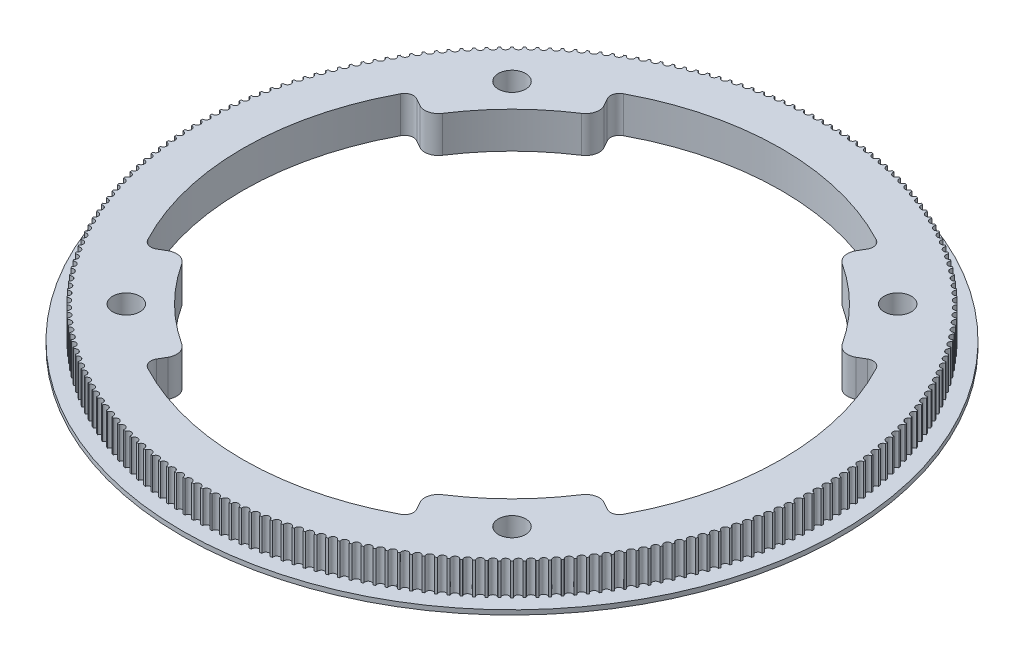
SolidWorks part; units mm, degrees
material "ABS"
ref_plane "Front Plane" through (0, 0, 0) normal (0, 0, 1) x (1, 0, 0)
ref_plane "Top Plane" through (0, 0, 0) normal (0, 1, 0) x (1, 0, 0)
ref_plane "Right Plane" through (0, 0, 0) normal (1, 0, 0) x (0, 0, -1)
sketch "Sketch1" plane through (0, 0, 0) normal (0, 1, 0) x (1, 0, 0)
  arc A0 (-0.76, 69.2508) -> (-1.2179, 69.2443) centre (0, 0) ccw
  arc A1 (-0.76, 69.2508) -> (0.76, 69.2508) centre (0, 69.255) ccw
  arc A2 (1.2179, 69.2443) -> (2.7372, 69.2009) centre (1.9776, 69.2268) ccw
  arc A3 (3.1947, 69.1813) -> (4.7122, 69.0945) centre (3.9537, 69.1421) ccw
  arc A4 (5.1689, 69.0618) -> (6.6833, 68.9318) centre (5.9265, 69.001) ccw
  arc A5 (7.139, 68.8861) -> (8.649, 68.7128) centre (7.8945, 68.8036) ccw
  arc A6 (9.1032, 68.6541) -> (10.6077, 68.4378) centre (9.856, 68.5501) ccw
  arc A7 (11.0599, 68.3662) -> (12.5577, 68.107) centre (11.8095, 68.2407) ccw
  arc A8 (13.0077, 68.0225) -> (14.4974, 67.7206) centre (13.7534, 67.8756) ccw
  arc A9 (14.9449, 67.6233) -> (16.4253, 67.279) centre (15.686, 67.4552) ccw
  arc A10 (16.8698, 67.1689) -> (18.3399, 66.7825) centre (17.6059, 66.9798) ccw
  arc A11 (18.781, 66.6598) -> (20.2394, 66.2316) centre (19.5114, 66.4497) ccw
  arc A12 (20.6769, 66.0963) -> (22.1225, 65.6266) centre (21.401, 65.8654) ccw
  arc A13 (22.5559, 65.4789) -> (23.9875, 64.9681) centre (23.2731, 65.2274) ccw
  arc A14 (24.4165, 64.8081) -> (25.8329, 64.2566) centre (25.1262, 64.5362) ccw
  arc A15 (26.2572, 64.0844) -> (27.6573, 63.4927) centre (26.9589, 63.7924) ccw
  arc A16 (28.0765, 63.3085) -> (29.4591, 62.6771) centre (28.7696, 62.9966) ccw
  arc A17 (29.8729, 62.4809) -> (31.2369, 61.8103) centre (30.5568, 62.1493) ccw
  arc A18 (31.6449, 61.6024) -> (32.9893, 60.8931) centre (32.319, 61.2514) ccw
  arc A19 (33.3912, 60.6736) -> (34.7147, 59.9262) centre (34.055, 60.3035) ccw
  arc A20 (35.1101, 59.6953) -> (36.4118, 58.9104) centre (35.7631, 59.3065) ccw
  arc A21 (36.8005, 58.6684) -> (38.0792, 57.8466) centre (37.4421, 58.261) ccw
  arc A22 (38.4608, 57.5936) -> (39.7155, 56.7356) centre (39.0905, 57.1681) ccw
  arc A23 (40.0898, 56.4718) -> (41.3195, 55.5784) centre (40.7071, 56.0285) ccw
  arc A24 (41.686, 55.304) -> (42.8897, 54.3758) centre (42.2904, 54.8432) ccw
  arc A25 (43.2483, 54.091) -> (44.425, 53.1289) centre (43.8393, 53.6132) ccw
  arc A26 (44.7753, 52.834) -> (45.924, 51.8386) centre (45.3524, 52.3394) ccw
  arc A27 (46.2658, 51.5338) -> (47.3856, 50.5061) centre (46.8285, 51.023) ccw
  arc A28 (47.7185, 50.1916) -> (48.8085, 49.1323) centre (48.2664, 49.665) ccw
  arc A29 (49.1323, 48.8085) -> (50.1916, 47.7185) centre (49.665, 48.2664) ccw
  arc A30 (50.5061, 47.3856) -> (51.5338, 46.2658) centre (51.023, 46.8285) ccw
  arc A31 (51.8386, 45.924) -> (52.834, 44.7753) centre (52.3394, 45.3524) ccw
  arc A32 (53.1289, 44.425) -> (54.091, 43.2483) centre (53.6132, 43.8393) ccw
  arc A33 (54.3758, 42.8897) -> (55.304, 41.686) centre (54.8432, 42.2904) ccw
  arc A34 (55.5784, 41.3195) -> (56.4718, 40.0898) centre (56.0285, 40.7071) ccw
  arc A35 (56.7356, 39.7155) -> (57.5936, 38.4608) centre (57.1681, 39.0905) ccw
  arc A36 (57.8466, 38.0792) -> (58.6684, 36.8005) centre (58.261, 37.4421) ccw
  arc A37 (58.9104, 36.4118) -> (59.6953, 35.1101) centre (59.3065, 35.7631) ccw
  arc A38 (59.9262, 34.7147) -> (60.6736, 33.3912) centre (60.3035, 34.055) ccw
  arc A39 (60.8931, 32.9893) -> (61.6024, 31.6449) centre (61.2514, 32.319) ccw
  arc A40 (61.8103, 31.2369) -> (62.4809, 29.8729) centre (62.1493, 30.5568) ccw
  arc A41 (62.6771, 29.4591) -> (63.3085, 28.0765) centre (62.9966, 28.7696) ccw
  arc A42 (63.4927, 27.6573) -> (64.0844, 26.2572) centre (63.7924, 26.9589) ccw
  arc A43 (64.2566, 25.8329) -> (64.8081, 24.4165) centre (64.5362, 25.1262) ccw
  arc A44 (64.9681, 23.9875) -> (65.4789, 22.5559) centre (65.2274, 23.2731) ccw
  arc A45 (65.6266, 22.1225) -> (66.0963, 20.6769) centre (65.8654, 21.401) ccw
  arc A46 (66.2316, 20.2394) -> (66.6598, 18.781) centre (66.4497, 19.5114) ccw
  arc A47 (66.7825, 18.3399) -> (67.1689, 16.8698) centre (66.9798, 17.6059) ccw
  arc A48 (67.279, 16.4253) -> (67.6233, 14.9449) centre (67.4552, 15.686) ccw
  arc A49 (67.7206, 14.4974) -> (68.0225, 13.0077) centre (67.8756, 13.7534) ccw
  arc A50 (68.107, 12.5577) -> (68.3662, 11.0599) centre (68.2407, 11.8095) ccw
  arc A51 (68.4378, 10.6077) -> (68.6541, 9.1032) centre (68.5501, 9.856) ccw
  arc A52 (68.7128, 8.649) -> (68.8861, 7.139) centre (68.8036, 7.8945) ccw
  arc A53 (68.9318, 6.6833) -> (69.0618, 5.1689) centre (69.001, 5.9265) ccw
  arc A54 (69.0945, 4.7122) -> (69.1813, 3.1947) centre (69.1421, 3.9537) ccw
  arc A55 (69.2009, 2.7372) -> (69.2443, 1.2179) centre (69.2268, 1.9776) ccw
  arc A56 (69.2508, 0.76) -> (69.2508, -0.76) centre (69.255, 0) ccw
  arc A57 (69.2443, -1.2179) -> (69.2009, -2.7372) centre (69.2268, -1.9776) ccw
  arc A58 (69.1813, -3.1947) -> (69.0945, -4.7122) centre (69.1421, -3.9537) ccw
  arc A59 (69.0618, -5.1689) -> (68.9318, -6.6833) centre (69.001, -5.9265) ccw
  arc A60 (68.8861, -7.139) -> (68.7128, -8.649) centre (68.8036, -7.8945) ccw
  arc A61 (68.6541, -9.1032) -> (68.4378, -10.6077) centre (68.5501, -9.856) ccw
  arc A62 (68.3662, -11.0599) -> (68.107, -12.5577) centre (68.2407, -11.8095) ccw
  arc A63 (68.0225, -13.0077) -> (67.7206, -14.4974) centre (67.8756, -13.7534) ccw
  arc A64 (67.6233, -14.9449) -> (67.279, -16.4253) centre (67.4552, -15.686) ccw
  arc A65 (67.1689, -16.8698) -> (66.7825, -18.3399) centre (66.9798, -17.6059) ccw
  arc A66 (66.6598, -18.781) -> (66.2316, -20.2394) centre (66.4497, -19.5114) ccw
  arc A67 (66.0963, -20.6769) -> (65.6266, -22.1225) centre (65.8654, -21.401) ccw
  arc A68 (65.4789, -22.5559) -> (64.9681, -23.9875) centre (65.2274, -23.2731) ccw
  arc A69 (64.8081, -24.4165) -> (64.2566, -25.8329) centre (64.5362, -25.1262) ccw
  arc A70 (64.0844, -26.2572) -> (63.4927, -27.6573) centre (63.7924, -26.9589) ccw
  arc A71 (63.3085, -28.0765) -> (62.6771, -29.4591) centre (62.9966, -28.7696) ccw
  arc A72 (62.4809, -29.8729) -> (61.8103, -31.2369) centre (62.1493, -30.5568) ccw
  arc A73 (61.6024, -31.6449) -> (60.8931, -32.9893) centre (61.2514, -32.319) ccw
  arc A74 (60.6736, -33.3912) -> (59.9262, -34.7147) centre (60.3035, -34.055) ccw
  arc A75 (59.6953, -35.1101) -> (58.9104, -36.4118) centre (59.3065, -35.7631) ccw
  arc A76 (58.6684, -36.8005) -> (57.8466, -38.0792) centre (58.261, -37.4421) ccw
  arc A77 (57.5936, -38.4608) -> (56.7356, -39.7155) centre (57.1681, -39.0905) ccw
  arc A78 (56.4718, -40.0898) -> (55.5784, -41.3195) centre (56.0285, -40.7071) ccw
  arc A79 (55.304, -41.686) -> (54.3758, -42.8897) centre (54.8432, -42.2904) ccw
  arc A80 (54.091, -43.2483) -> (53.1289, -44.425) centre (53.6132, -43.8393) ccw
  arc A81 (52.834, -44.7753) -> (51.8386, -45.924) centre (52.3394, -45.3524) ccw
  arc A82 (51.5338, -46.2658) -> (50.5061, -47.3856) centre (51.023, -46.8285) ccw
  arc A83 (50.1916, -47.7185) -> (49.1323, -48.8085) centre (49.665, -48.2664) ccw
  arc A84 (48.8085, -49.1323) -> (47.7185, -50.1916) centre (48.2664, -49.665) ccw
  arc A85 (47.3856, -50.5061) -> (46.2658, -51.5338) centre (46.8285, -51.023) ccw
  arc A86 (45.924, -51.8386) -> (44.7753, -52.834) centre (45.3524, -52.3394) ccw
  arc A87 (44.425, -53.1289) -> (43.2483, -54.091) centre (43.8393, -53.6132) ccw
  arc A88 (42.8897, -54.3758) -> (41.686, -55.304) centre (42.2904, -54.8432) ccw
  arc A89 (41.3195, -55.5784) -> (40.0898, -56.4718) centre (40.7071, -56.0285) ccw
  arc A90 (39.7155, -56.7356) -> (38.4608, -57.5936) centre (39.0905, -57.1681) ccw
  arc A91 (38.0792, -57.8466) -> (36.8005, -58.6684) centre (37.4421, -58.261) ccw
  arc A92 (36.4118, -58.9104) -> (35.1101, -59.6953) centre (35.7631, -59.3065) ccw
  arc A93 (34.7147, -59.9262) -> (33.3912, -60.6736) centre (34.055, -60.3035) ccw
  arc A94 (32.9893, -60.8931) -> (31.6449, -61.6024) centre (32.319, -61.2514) ccw
  arc A95 (31.2369, -61.8103) -> (29.8729, -62.4809) centre (30.5568, -62.1493) ccw
  arc A96 (29.4591, -62.6771) -> (28.0765, -63.3085) centre (28.7696, -62.9966) ccw
  arc A97 (27.6573, -63.4927) -> (26.2572, -64.0844) centre (26.9589, -63.7924) ccw
  arc A98 (25.8329, -64.2566) -> (24.4165, -64.8081) centre (25.1262, -64.5362) ccw
  arc A99 (23.9875, -64.9681) -> (22.5559, -65.4789) centre (23.2731, -65.2274) ccw
  arc A100 (22.1225, -65.6266) -> (20.6769, -66.0963) centre (21.401, -65.8654) ccw
  arc A101 (20.2394, -66.2316) -> (18.781, -66.6598) centre (19.5114, -66.4497) ccw
  arc A102 (18.3399, -66.7825) -> (16.8698, -67.1689) centre (17.6059, -66.9798) ccw
  arc A103 (16.4253, -67.279) -> (14.9449, -67.6233) centre (15.686, -67.4552) ccw
  arc A104 (14.4974, -67.7206) -> (13.0077, -68.0225) centre (13.7534, -67.8756) ccw
  arc A105 (12.5577, -68.107) -> (11.0599, -68.3662) centre (11.8095, -68.2407) ccw
  arc A106 (10.6077, -68.4378) -> (9.1032, -68.6541) centre (9.856, -68.5501) ccw
  arc A107 (8.649, -68.7128) -> (7.139, -68.8861) centre (7.8945, -68.8036) ccw
  arc A108 (6.6833, -68.9318) -> (5.1689, -69.0618) centre (5.9265, -69.001) ccw
  arc A109 (4.7122, -69.0945) -> (3.1947, -69.1813) centre (3.9537, -69.1421) ccw
  arc A110 (2.7372, -69.2009) -> (1.2179, -69.2443) centre (1.9776, -69.2268) ccw
  arc A111 (0.76, -69.2508) -> (-0.76, -69.2508) centre (0, -69.255) ccw
  arc A112 (-1.2179, -69.2443) -> (-2.7372, -69.2009) centre (-1.9776, -69.2268) ccw
  arc A113 (-3.1947, -69.1813) -> (-4.7122, -69.0945) centre (-3.9537, -69.1421) ccw
  arc A114 (-5.1689, -69.0618) -> (-6.6833, -68.9318) centre (-5.9265, -69.001) ccw
  arc A115 (-7.139, -68.8861) -> (-8.649, -68.7128) centre (-7.8945, -68.8036) ccw
  arc A116 (-9.1032, -68.6541) -> (-10.6077, -68.4378) centre (-9.856, -68.5501) ccw
  arc A117 (-11.0599, -68.3662) -> (-12.5577, -68.107) centre (-11.8095, -68.2407) ccw
  arc A118 (-13.0077, -68.0225) -> (-14.4974, -67.7206) centre (-13.7534, -67.8756) ccw
  arc A119 (-14.9449, -67.6233) -> (-16.4253, -67.279) centre (-15.686, -67.4552) ccw
  arc A120 (-16.8698, -67.1689) -> (-18.3399, -66.7825) centre (-17.6059, -66.9798) ccw
  arc A121 (-18.781, -66.6598) -> (-20.2394, -66.2316) centre (-19.5114, -66.4497) ccw
  arc A122 (-20.6769, -66.0963) -> (-22.1225, -65.6266) centre (-21.401, -65.8654) ccw
  arc A123 (-22.5559, -65.4789) -> (-23.9875, -64.9681) centre (-23.2731, -65.2274) ccw
  arc A124 (-24.4165, -64.8081) -> (-25.8329, -64.2566) centre (-25.1262, -64.5362) ccw
  arc A125 (-26.2572, -64.0844) -> (-27.6573, -63.4927) centre (-26.9589, -63.7924) ccw
  arc A126 (-28.0765, -63.3085) -> (-29.4591, -62.6771) centre (-28.7696, -62.9966) ccw
  arc A127 (-29.8729, -62.4809) -> (-31.2369, -61.8103) centre (-30.5568, -62.1493) ccw
  arc A128 (-31.6449, -61.6024) -> (-32.9893, -60.8931) centre (-32.319, -61.2514) ccw
  arc A129 (-33.3912, -60.6736) -> (-34.7147, -59.9262) centre (-34.055, -60.3035) ccw
  arc A130 (-35.1101, -59.6953) -> (-36.4118, -58.9104) centre (-35.7631, -59.3065) ccw
  arc A131 (-36.8005, -58.6684) -> (-38.0792, -57.8466) centre (-37.4421, -58.261) ccw
  arc A132 (-38.4608, -57.5936) -> (-39.7155, -56.7356) centre (-39.0905, -57.1681) ccw
  arc A133 (-40.0898, -56.4718) -> (-41.3195, -55.5784) centre (-40.7071, -56.0285) ccw
  arc A134 (-41.686, -55.304) -> (-42.8897, -54.3758) centre (-42.2904, -54.8432) ccw
  arc A135 (-43.2483, -54.091) -> (-44.425, -53.1289) centre (-43.8393, -53.6132) ccw
  arc A136 (-44.7753, -52.834) -> (-45.924, -51.8386) centre (-45.3524, -52.3394) ccw
  arc A137 (-46.2658, -51.5338) -> (-47.3856, -50.5061) centre (-46.8285, -51.023) ccw
  arc A138 (-47.7185, -50.1916) -> (-48.8085, -49.1323) centre (-48.2664, -49.665) ccw
  arc A139 (-49.1323, -48.8085) -> (-50.1916, -47.7185) centre (-49.665, -48.2664) ccw
  arc A140 (-50.5061, -47.3856) -> (-51.5338, -46.2658) centre (-51.023, -46.8285) ccw
  arc A141 (-51.8386, -45.924) -> (-52.834, -44.7753) centre (-52.3394, -45.3524) ccw
  arc A142 (-53.1289, -44.425) -> (-54.091, -43.2483) centre (-53.6132, -43.8393) ccw
  arc A143 (-54.3758, -42.8897) -> (-55.304, -41.686) centre (-54.8432, -42.2904) ccw
  arc A144 (-55.5784, -41.3195) -> (-56.4718, -40.0898) centre (-56.0285, -40.7071) ccw
  arc A145 (-56.7356, -39.7155) -> (-57.5936, -38.4608) centre (-57.1681, -39.0905) ccw
  arc A146 (-57.8466, -38.0792) -> (-58.6684, -36.8005) centre (-58.261, -37.4421) ccw
  arc A147 (-58.9104, -36.4118) -> (-59.6953, -35.1101) centre (-59.3065, -35.7631) ccw
  arc A148 (-59.9262, -34.7147) -> (-60.6736, -33.3912) centre (-60.3035, -34.055) ccw
  arc A149 (-60.8931, -32.9893) -> (-61.6024, -31.6449) centre (-61.2514, -32.319) ccw
  arc A150 (-61.8103, -31.2369) -> (-62.4809, -29.8729) centre (-62.1493, -30.5568) ccw
  arc A151 (-62.6771, -29.4591) -> (-63.3085, -28.0765) centre (-62.9966, -28.7696) ccw
  arc A152 (-63.4927, -27.6573) -> (-64.0844, -26.2572) centre (-63.7924, -26.9589) ccw
  arc A153 (-64.2566, -25.8329) -> (-64.8081, -24.4165) centre (-64.5362, -25.1262) ccw
  arc A154 (-64.9681, -23.9875) -> (-65.4789, -22.5559) centre (-65.2274, -23.2731) ccw
  arc A155 (-65.6266, -22.1225) -> (-66.0963, -20.6769) centre (-65.8654, -21.401) ccw
  arc A156 (-66.2316, -20.2394) -> (-66.6598, -18.781) centre (-66.4497, -19.5114) ccw
  arc A157 (-66.7825, -18.3399) -> (-67.1689, -16.8698) centre (-66.9798, -17.6059) ccw
  arc A158 (-67.279, -16.4253) -> (-67.6233, -14.9449) centre (-67.4552, -15.686) ccw
  arc A159 (-67.7206, -14.4974) -> (-68.0225, -13.0077) centre (-67.8756, -13.7534) ccw
  arc A160 (-68.107, -12.5577) -> (-68.3662, -11.0599) centre (-68.2407, -11.8095) ccw
  arc A161 (-68.4378, -10.6077) -> (-68.6541, -9.1032) centre (-68.5501, -9.856) ccw
  arc A162 (-68.7128, -8.649) -> (-68.8861, -7.139) centre (-68.8036, -7.8945) ccw
  arc A163 (-68.9318, -6.6833) -> (-69.0618, -5.1689) centre (-69.001, -5.9265) ccw
  arc A164 (-69.0945, -4.7122) -> (-69.1813, -3.1947) centre (-69.1421, -3.9537) ccw
  arc A165 (-69.2009, -2.7372) -> (-69.2443, -1.2179) centre (-69.2268, -1.9776) ccw
  arc A166 (-69.2508, -0.76) -> (-69.2508, 0.76) centre (-69.255, 0) ccw
  arc A167 (-69.2443, 1.2179) -> (-69.2009, 2.7372) centre (-69.2268, 1.9776) ccw
  arc A168 (-69.1813, 3.1947) -> (-69.0945, 4.7122) centre (-69.1421, 3.9537) ccw
  arc A169 (-69.0618, 5.1689) -> (-68.9318, 6.6833) centre (-69.001, 5.9265) ccw
  arc A170 (-68.8861, 7.139) -> (-68.7128, 8.649) centre (-68.8036, 7.8945) ccw
  arc A171 (-68.6541, 9.1032) -> (-68.4378, 10.6077) centre (-68.5501, 9.856) ccw
  arc A172 (-68.3662, 11.0599) -> (-68.107, 12.5577) centre (-68.2407, 11.8095) ccw
  arc A173 (-68.0225, 13.0077) -> (-67.7206, 14.4974) centre (-67.8756, 13.7534) ccw
  arc A174 (-67.6233, 14.9449) -> (-67.279, 16.4253) centre (-67.4552, 15.686) ccw
  arc A175 (-67.1689, 16.8698) -> (-66.7825, 18.3399) centre (-66.9798, 17.6059) ccw
  arc A176 (-66.6598, 18.781) -> (-66.2316, 20.2394) centre (-66.4497, 19.5114) ccw
  arc A177 (-66.0963, 20.6769) -> (-65.6266, 22.1225) centre (-65.8654, 21.401) ccw
  arc A178 (-65.4789, 22.5559) -> (-64.9681, 23.9875) centre (-65.2274, 23.2731) ccw
  arc A179 (-64.8081, 24.4165) -> (-64.2566, 25.8329) centre (-64.5362, 25.1262) ccw
  arc A180 (-64.0844, 26.2572) -> (-63.4927, 27.6573) centre (-63.7924, 26.9589) ccw
  arc A181 (-63.3085, 28.0765) -> (-62.6771, 29.4591) centre (-62.9966, 28.7696) ccw
  arc A182 (-62.4809, 29.8729) -> (-61.8103, 31.2369) centre (-62.1493, 30.5568) ccw
  arc A183 (-61.6024, 31.6449) -> (-60.8931, 32.9893) centre (-61.2514, 32.319) ccw
  arc A184 (-60.6736, 33.3912) -> (-59.9262, 34.7147) centre (-60.3035, 34.055) ccw
  arc A185 (-59.6953, 35.1101) -> (-58.9104, 36.4118) centre (-59.3065, 35.7631) ccw
  arc A186 (-58.6684, 36.8005) -> (-57.8466, 38.0792) centre (-58.261, 37.4421) ccw
  arc A187 (-57.5936, 38.4608) -> (-56.7356, 39.7155) centre (-57.1681, 39.0905) ccw
  arc A188 (-56.4718, 40.0898) -> (-55.5784, 41.3195) centre (-56.0285, 40.7071) ccw
  arc A189 (-55.304, 41.686) -> (-54.3758, 42.8897) centre (-54.8432, 42.2904) ccw
  arc A190 (-54.091, 43.2483) -> (-53.1289, 44.425) centre (-53.6132, 43.8393) ccw
  arc A191 (-52.834, 44.7753) -> (-51.8386, 45.924) centre (-52.3394, 45.3524) ccw
  arc A192 (-51.5338, 46.2658) -> (-50.5061, 47.3856) centre (-51.023, 46.8285) ccw
  arc A193 (-50.1916, 47.7185) -> (-49.1323, 48.8085) centre (-49.665, 48.2664) ccw
  arc A194 (-48.8085, 49.1323) -> (-47.7185, 50.1916) centre (-48.2664, 49.665) ccw
  arc A195 (-47.3856, 50.5061) -> (-46.2658, 51.5338) centre (-46.8285, 51.023) ccw
  arc A196 (-45.924, 51.8386) -> (-44.7753, 52.834) centre (-45.3524, 52.3394) ccw
  arc A197 (-44.425, 53.1289) -> (-43.2483, 54.091) centre (-43.8393, 53.6132) ccw
  arc A198 (-42.8897, 54.3758) -> (-41.686, 55.304) centre (-42.2904, 54.8432) ccw
  arc A199 (-41.3195, 55.5784) -> (-40.0898, 56.4718) centre (-40.7071, 56.0285) ccw
  arc A200 (-39.7155, 56.7356) -> (-38.4608, 57.5936) centre (-39.0905, 57.1681) ccw
  arc A201 (-38.0792, 57.8466) -> (-36.8005, 58.6684) centre (-37.4421, 58.261) ccw
  arc A202 (-36.4118, 58.9104) -> (-35.1101, 59.6953) centre (-35.7631, 59.3065) ccw
  arc A203 (-34.7147, 59.9262) -> (-33.3912, 60.6736) centre (-34.055, 60.3035) ccw
  arc A204 (-32.9893, 60.8931) -> (-31.6449, 61.6024) centre (-32.319, 61.2514) ccw
  arc A205 (-31.2369, 61.8103) -> (-29.8729, 62.4809) centre (-30.5568, 62.1493) ccw
  arc A206 (-29.4591, 62.6771) -> (-28.0765, 63.3085) centre (-28.7696, 62.9966) ccw
  arc A207 (-27.6573, 63.4927) -> (-26.2572, 64.0844) centre (-26.9589, 63.7924) ccw
  arc A208 (-25.8329, 64.2566) -> (-24.4165, 64.8081) centre (-25.1262, 64.5362) ccw
  arc A209 (-23.9875, 64.9681) -> (-22.5559, 65.4789) centre (-23.2731, 65.2274) ccw
  arc A210 (-22.1225, 65.6266) -> (-20.6769, 66.0963) centre (-21.401, 65.8654) ccw
  arc A211 (-20.2394, 66.2316) -> (-18.781, 66.6598) centre (-19.5114, 66.4497) ccw
  arc A212 (-18.3399, 66.7825) -> (-16.8698, 67.1689) centre (-17.6059, 66.9798) ccw
  arc A213 (-16.4253, 67.279) -> (-14.9449, 67.6233) centre (-15.686, 67.4552) ccw
  arc A214 (-14.4974, 67.7206) -> (-13.0077, 68.0225) centre (-13.7534, 67.8756) ccw
  arc A215 (-12.5577, 68.107) -> (-11.0599, 68.3662) centre (-11.8095, 68.2407) ccw
  arc A216 (-10.6077, 68.4378) -> (-9.1032, 68.6541) centre (-9.856, 68.5501) ccw
  arc A217 (-8.649, 68.7128) -> (-7.139, 68.8861) centre (-7.8945, 68.8036) ccw
  arc A218 (-6.6833, 68.9318) -> (-5.1689, 69.0618) centre (-5.9265, 69.001) ccw
  arc A219 (-4.7122, 69.0945) -> (-3.1947, 69.1813) centre (-3.9537, 69.1421) ccw
  arc A220 (-2.7372, 69.2009) -> (-1.2179, 69.2443) centre (-1.9776, 69.2268) ccw
  arc A221 (1.2179, 69.2443) -> (0.76, 69.2508) centre (0, 0) ccw
  arc A222 (3.1947, 69.1813) -> (2.7372, 69.2009) centre (0, 0) ccw
  arc A223 (5.1689, 69.0618) -> (4.7122, 69.0945) centre (0, 0) ccw
  arc A224 (7.139, 68.8861) -> (6.6833, 68.9318) centre (0, 0) ccw
  arc A225 (9.1032, 68.6541) -> (8.649, 68.7128) centre (0, 0) ccw
  arc A226 (11.0599, 68.3662) -> (10.6077, 68.4378) centre (0, 0) ccw
  arc A227 (13.0077, 68.0225) -> (12.5577, 68.107) centre (0, 0) ccw
  arc A228 (14.9449, 67.6233) -> (14.4974, 67.7206) centre (0, 0) ccw
  arc A229 (16.8698, 67.1689) -> (16.4253, 67.279) centre (0, 0) ccw
  arc A230 (18.781, 66.6598) -> (18.3399, 66.7825) centre (0, 0) ccw
  arc A231 (20.6769, 66.0963) -> (20.2394, 66.2316) centre (0, 0) ccw
  arc A232 (22.5559, 65.4789) -> (22.1225, 65.6266) centre (0, 0) ccw
  arc A233 (24.4165, 64.8081) -> (23.9875, 64.9681) centre (0, 0) ccw
  arc A234 (26.2572, 64.0844) -> (25.8329, 64.2566) centre (0, 0) ccw
  arc A235 (28.0765, 63.3085) -> (27.6573, 63.4927) centre (0, 0) ccw
  arc A236 (29.8729, 62.4809) -> (29.4591, 62.6771) centre (0, 0) ccw
  arc A237 (31.6449, 61.6024) -> (31.2369, 61.8103) centre (0, 0) ccw
  arc A238 (33.3912, 60.6736) -> (32.9893, 60.8931) centre (0, 0) ccw
  arc A239 (35.1101, 59.6953) -> (34.7147, 59.9262) centre (0, 0) ccw
  arc A240 (36.8005, 58.6684) -> (36.4118, 58.9104) centre (0, 0) ccw
  arc A241 (38.4608, 57.5936) -> (38.0792, 57.8466) centre (0, 0) ccw
  arc A242 (40.0898, 56.4718) -> (39.7155, 56.7356) centre (0, 0) ccw
  arc A243 (41.686, 55.304) -> (41.3195, 55.5784) centre (0, 0) ccw
  arc A244 (43.2483, 54.091) -> (42.8897, 54.3758) centre (0, 0) ccw
  arc A245 (44.7753, 52.834) -> (44.425, 53.1289) centre (0, 0) ccw
  arc A246 (46.2658, 51.5338) -> (45.924, 51.8386) centre (0, 0) ccw
  arc A247 (47.7185, 50.1916) -> (47.3856, 50.5061) centre (0, 0) ccw
  arc A248 (49.1323, 48.8085) -> (48.8085, 49.1323) centre (0, 0) ccw
  arc A249 (50.5061, 47.3856) -> (50.1916, 47.7185) centre (0, 0) ccw
  arc A250 (51.8386, 45.924) -> (51.5338, 46.2658) centre (0, 0) ccw
  arc A251 (53.1289, 44.425) -> (52.834, 44.7753) centre (0, 0) ccw
  arc A252 (54.3758, 42.8897) -> (54.091, 43.2483) centre (0, 0) ccw
  arc A253 (55.5784, 41.3195) -> (55.304, 41.686) centre (0, 0) ccw
  arc A254 (56.7356, 39.7155) -> (56.4718, 40.0898) centre (0, 0) ccw
  arc A255 (57.8466, 38.0792) -> (57.5936, 38.4608) centre (0, 0) ccw
  arc A256 (58.9104, 36.4118) -> (58.6684, 36.8005) centre (0, 0) ccw
  arc A257 (59.9262, 34.7147) -> (59.6953, 35.1101) centre (0, 0) ccw
  arc A258 (60.8931, 32.9893) -> (60.6736, 33.3912) centre (0, 0) ccw
  arc A259 (61.8103, 31.2369) -> (61.6024, 31.6449) centre (0, 0) ccw
  arc A260 (62.6771, 29.4591) -> (62.4809, 29.8729) centre (0, 0) ccw
  arc A261 (63.4927, 27.6573) -> (63.3085, 28.0765) centre (0, 0) ccw
  arc A262 (64.2566, 25.8329) -> (64.0844, 26.2572) centre (0, 0) ccw
  arc A263 (64.9681, 23.9875) -> (64.8081, 24.4165) centre (0, 0) ccw
  arc A264 (65.6266, 22.1225) -> (65.4789, 22.5559) centre (0, 0) ccw
  arc A265 (66.2316, 20.2394) -> (66.0963, 20.6769) centre (0, 0) ccw
  arc A266 (66.7825, 18.3399) -> (66.6598, 18.781) centre (0, 0) ccw
  arc A267 (67.279, 16.4253) -> (67.1689, 16.8698) centre (0, 0) ccw
  arc A268 (67.7206, 14.4974) -> (67.6233, 14.9449) centre (0, 0) ccw
  arc A269 (68.107, 12.5577) -> (68.0225, 13.0077) centre (0, 0) ccw
  arc A270 (68.4378, 10.6077) -> (68.3662, 11.0599) centre (0, 0) ccw
  arc A271 (68.7128, 8.649) -> (68.6541, 9.1032) centre (0, 0) ccw
  arc A272 (68.9318, 6.6833) -> (68.8861, 7.139) centre (0, 0) ccw
  arc A273 (69.0945, 4.7122) -> (69.0618, 5.1689) centre (0, 0) ccw
  arc A274 (69.2009, 2.7372) -> (69.1813, 3.1947) centre (0, 0) ccw
  arc A275 (69.2508, 0.76) -> (69.2443, 1.2179) centre (0, 0) ccw
  arc A276 (69.2443, -1.2179) -> (69.2508, -0.76) centre (0, 0) ccw
  arc A277 (69.1813, -3.1947) -> (69.2009, -2.7372) centre (0, 0) ccw
  arc A278 (69.0618, -5.1689) -> (69.0945, -4.7122) centre (0, 0) ccw
  arc A279 (68.8861, -7.139) -> (68.9318, -6.6833) centre (0, 0) ccw
  arc A280 (68.6541, -9.1032) -> (68.7128, -8.649) centre (0, 0) ccw
  arc A281 (68.3662, -11.0599) -> (68.4378, -10.6077) centre (0, 0) ccw
  arc A282 (68.0225, -13.0077) -> (68.107, -12.5577) centre (0, 0) ccw
  arc A283 (67.6233, -14.9449) -> (67.7206, -14.4974) centre (0, 0) ccw
  arc A284 (67.1689, -16.8698) -> (67.279, -16.4253) centre (0, 0) ccw
  arc A285 (66.6598, -18.781) -> (66.7825, -18.3399) centre (0, 0) ccw
  arc A286 (66.0963, -20.6769) -> (66.2316, -20.2394) centre (0, 0) ccw
  arc A287 (65.4789, -22.5559) -> (65.6266, -22.1225) centre (0, 0) ccw
  arc A288 (64.8081, -24.4165) -> (64.9681, -23.9875) centre (0, 0) ccw
  arc A289 (64.0844, -26.2572) -> (64.2566, -25.8329) centre (0, 0) ccw
  arc A290 (63.3085, -28.0765) -> (63.4927, -27.6573) centre (0, 0) ccw
  arc A291 (62.4809, -29.8729) -> (62.6771, -29.4591) centre (0, 0) ccw
  arc A292 (61.6024, -31.6449) -> (61.8103, -31.2369) centre (0, 0) ccw
  arc A293 (60.6736, -33.3912) -> (60.8931, -32.9893) centre (0, 0) ccw
  arc A294 (59.6953, -35.1101) -> (59.9262, -34.7147) centre (0, 0) ccw
  arc A295 (58.6684, -36.8005) -> (58.9104, -36.4118) centre (0, 0) ccw
  arc A296 (57.5936, -38.4608) -> (57.8466, -38.0792) centre (0, 0) ccw
  arc A297 (56.4718, -40.0898) -> (56.7356, -39.7155) centre (0, 0) ccw
  arc A298 (55.304, -41.686) -> (55.5784, -41.3195) centre (0, 0) ccw
  arc A299 (54.091, -43.2483) -> (54.3758, -42.8897) centre (0, 0) ccw
  arc A300 (52.834, -44.7753) -> (53.1289, -44.425) centre (0, 0) ccw
  arc A301 (51.5338, -46.2658) -> (51.8386, -45.924) centre (0, 0) ccw
  arc A302 (50.1916, -47.7185) -> (50.5061, -47.3856) centre (0, 0) ccw
  arc A303 (48.8085, -49.1323) -> (49.1323, -48.8085) centre (0, 0) ccw
  arc A304 (47.3856, -50.5061) -> (47.7185, -50.1916) centre (0, 0) ccw
  arc A305 (45.924, -51.8386) -> (46.2658, -51.5338) centre (0, 0) ccw
  arc A306 (44.425, -53.1289) -> (44.7753, -52.834) centre (0, 0) ccw
  arc A307 (42.8897, -54.3758) -> (43.2483, -54.091) centre (0, 0) ccw
  arc A308 (41.3195, -55.5784) -> (41.686, -55.304) centre (0, 0) ccw
  arc A309 (39.7155, -56.7356) -> (40.0898, -56.4718) centre (0, 0) ccw
  arc A310 (38.0792, -57.8466) -> (38.4608, -57.5936) centre (0, 0) ccw
  arc A311 (36.4118, -58.9104) -> (36.8005, -58.6684) centre (0, 0) ccw
  arc A312 (34.7147, -59.9262) -> (35.1101, -59.6953) centre (0, 0) ccw
  arc A313 (32.9893, -60.8931) -> (33.3912, -60.6736) centre (0, 0) ccw
  arc A314 (31.2369, -61.8103) -> (31.6449, -61.6024) centre (0, 0) ccw
  arc A315 (29.4591, -62.6771) -> (29.8729, -62.4809) centre (0, 0) ccw
  arc A316 (27.6573, -63.4927) -> (28.0765, -63.3085) centre (0, 0) ccw
  arc A317 (23.9875, -64.9681) -> (24.4165, -64.8081) centre (0, 0) ccw
  arc A318 (25.8329, -64.2566) -> (26.2572, -64.0844) centre (0, 0) ccw
  arc A319 (22.1225, -65.6266) -> (22.5559, -65.4789) centre (0, 0) ccw
  arc A320 (20.2394, -66.2316) -> (20.6769, -66.0963) centre (0, 0) ccw
  arc A321 (18.3399, -66.7825) -> (18.781, -66.6598) centre (0, 0) ccw
  arc A322 (16.4253, -67.279) -> (16.8698, -67.1689) centre (0, 0) ccw
  arc A323 (14.4974, -67.7206) -> (14.9449, -67.6233) centre (0, 0) ccw
  arc A324 (12.5577, -68.107) -> (13.0077, -68.0225) centre (0, 0) ccw
  arc A325 (10.6077, -68.4378) -> (11.0599, -68.3662) centre (0, 0) ccw
  arc A326 (8.649, -68.7128) -> (9.1032, -68.6541) centre (0, 0) ccw
  arc A327 (6.6833, -68.9318) -> (7.139, -68.8861) centre (0, 0) ccw
  arc A328 (4.7122, -69.0945) -> (5.1689, -69.0618) centre (0, 0) ccw
  arc A329 (2.7372, -69.2009) -> (3.1947, -69.1813) centre (0, 0) ccw
  arc A330 (0.76, -69.2508) -> (1.2179, -69.2443) centre (0, 0) ccw
  arc A331 (-1.2179, -69.2443) -> (-0.76, -69.2508) centre (0, 0) ccw
  arc A332 (-3.1947, -69.1813) -> (-2.7372, -69.2009) centre (0, 0) ccw
  arc A333 (-5.1689, -69.0618) -> (-4.7122, -69.0945) centre (0, 0) ccw
  arc A334 (-7.139, -68.8861) -> (-6.6833, -68.9318) centre (0, 0) ccw
  arc A335 (-9.1032, -68.6541) -> (-8.649, -68.7128) centre (0, 0) ccw
  arc A336 (-11.0599, -68.3662) -> (-10.6077, -68.4378) centre (0, 0) ccw
  arc A337 (-13.0077, -68.0225) -> (-12.5577, -68.107) centre (0, 0) ccw
  arc A338 (-14.9449, -67.6233) -> (-14.4974, -67.7206) centre (0, 0) ccw
  arc A339 (-16.8698, -67.1689) -> (-16.4253, -67.279) centre (0, 0) ccw
  arc A340 (-18.781, -66.6598) -> (-18.3399, -66.7825) centre (0, 0) ccw
  arc A341 (-20.6769, -66.0963) -> (-20.2394, -66.2316) centre (0, 0) ccw
  arc A342 (-22.5559, -65.4789) -> (-22.1225, -65.6266) centre (0, 0) ccw
  arc A343 (-24.4165, -64.8081) -> (-23.9875, -64.9681) centre (0, 0) ccw
  arc A344 (-26.2572, -64.0844) -> (-25.8329, -64.2566) centre (0, 0) ccw
  arc A345 (-28.0765, -63.3085) -> (-27.6573, -63.4927) centre (0, 0) ccw
  arc A346 (-29.8729, -62.4809) -> (-29.4591, -62.6771) centre (0, 0) ccw
  arc A347 (-31.6449, -61.6024) -> (-31.2369, -61.8103) centre (0, 0) ccw
  arc A348 (-33.3912, -60.6736) -> (-32.9893, -60.8931) centre (0, 0) ccw
  arc A349 (-35.1101, -59.6953) -> (-34.7147, -59.9262) centre (0, 0) ccw
  arc A350 (-36.8005, -58.6684) -> (-36.4118, -58.9104) centre (0, 0) ccw
  arc A351 (-38.4608, -57.5936) -> (-38.0792, -57.8466) centre (0, 0) ccw
  arc A352 (-40.0898, -56.4718) -> (-39.7155, -56.7356) centre (0, 0) ccw
  arc A353 (-41.686, -55.304) -> (-41.3195, -55.5784) centre (0, 0) ccw
  arc A354 (-43.2483, -54.091) -> (-42.8897, -54.3758) centre (0, 0) ccw
  arc A355 (-44.7753, -52.834) -> (-44.425, -53.1289) centre (0, 0) ccw
  arc A356 (-46.2658, -51.5338) -> (-45.924, -51.8386) centre (0, 0) ccw
  arc A357 (-47.7185, -50.1916) -> (-47.3856, -50.5061) centre (0, 0) ccw
  arc A358 (-49.1323, -48.8085) -> (-48.8085, -49.1323) centre (0, 0) ccw
  arc A359 (-50.5061, -47.3856) -> (-50.1916, -47.7185) centre (0, 0) ccw
  arc A360 (-51.8386, -45.924) -> (-51.5338, -46.2658) centre (0, 0) ccw
  arc A361 (-53.1289, -44.425) -> (-52.834, -44.7753) centre (0, 0) ccw
  arc A362 (-54.3758, -42.8897) -> (-54.091, -43.2483) centre (0, 0) ccw
  arc A363 (-55.5784, -41.3195) -> (-55.304, -41.686) centre (0, 0) ccw
  arc A364 (-56.7356, -39.7155) -> (-56.4718, -40.0898) centre (0, 0) ccw
  arc A365 (-57.8466, -38.0792) -> (-57.5936, -38.4608) centre (0, 0) ccw
  arc A366 (-58.9104, -36.4118) -> (-58.6684, -36.8005) centre (0, 0) ccw
  arc A367 (-59.9262, -34.7147) -> (-59.6953, -35.1101) centre (0, 0) ccw
  arc A368 (-60.8931, -32.9893) -> (-60.6736, -33.3912) centre (0, 0) ccw
  arc A369 (-61.8103, -31.2369) -> (-61.6024, -31.6449) centre (0, 0) ccw
  arc A370 (-62.6771, -29.4591) -> (-62.4809, -29.8729) centre (0, 0) ccw
  arc A371 (-63.4927, -27.6573) -> (-63.3085, -28.0765) centre (0, 0) ccw
  arc A372 (-64.2566, -25.8329) -> (-64.0844, -26.2572) centre (0, 0) ccw
  arc A373 (-64.9681, -23.9875) -> (-64.8081, -24.4165) centre (0, 0) ccw
  arc A374 (-65.6266, -22.1225) -> (-65.4789, -22.5559) centre (0, 0) ccw
  arc A375 (-66.2316, -20.2394) -> (-66.0963, -20.6769) centre (0, 0) ccw
  arc A376 (-66.7825, -18.3399) -> (-66.6598, -18.781) centre (0, 0) ccw
  arc A377 (-67.279, -16.4253) -> (-67.1689, -16.8698) centre (0, 0) ccw
  arc A378 (-67.7206, -14.4974) -> (-67.6233, -14.9449) centre (0, 0) ccw
  arc A379 (-68.107, -12.5577) -> (-68.0225, -13.0077) centre (0, 0) ccw
  arc A380 (-68.4378, -10.6077) -> (-68.3662, -11.0599) centre (0, 0) ccw
  arc A381 (-68.7128, -8.649) -> (-68.6541, -9.1032) centre (0, 0) ccw
  arc A382 (-68.9318, -6.6833) -> (-68.8861, -7.139) centre (0, 0) ccw
  arc A383 (-69.0945, -4.7122) -> (-69.0618, -5.1689) centre (0, 0) ccw
  arc A384 (-69.2009, -2.7372) -> (-69.1813, -3.1947) centre (0, 0) ccw
  arc A385 (-69.2508, -0.76) -> (-69.2443, -1.2179) centre (0, 0) ccw
  arc A386 (-69.2443, 1.2179) -> (-69.2508, 0.76) centre (0, 0) ccw
  arc A387 (-69.1813, 3.1947) -> (-69.2009, 2.7372) centre (0, 0) ccw
  arc A388 (-69.0618, 5.1689) -> (-69.0945, 4.7122) centre (0, 0) ccw
  arc A389 (-68.8861, 7.139) -> (-68.9318, 6.6833) centre (0, 0) ccw
  arc A390 (-68.6541, 9.1032) -> (-68.7128, 8.649) centre (0, 0) ccw
  arc A391 (-68.3662, 11.0599) -> (-68.4378, 10.6077) centre (0, 0) ccw
  arc A392 (-68.0225, 13.0077) -> (-68.107, 12.5577) centre (0, 0) ccw
  arc A393 (-67.6233, 14.9449) -> (-67.7206, 14.4974) centre (0, 0) ccw
  arc A394 (-67.1689, 16.8698) -> (-67.279, 16.4253) centre (0, 0) ccw
  arc A395 (-66.6598, 18.781) -> (-66.7825, 18.3399) centre (0, 0) ccw
  arc A396 (-66.0963, 20.6769) -> (-66.2316, 20.2394) centre (0, 0) ccw
  arc A397 (-65.4789, 22.5559) -> (-65.6266, 22.1225) centre (0, 0) ccw
  arc A398 (-64.8081, 24.4165) -> (-64.9681, 23.9875) centre (0, 0) ccw
  arc A399 (-64.0844, 26.2572) -> (-64.2566, 25.8329) centre (0, 0) ccw
  arc A400 (-63.3085, 28.0765) -> (-63.4927, 27.6573) centre (0, 0) ccw
  arc A401 (-62.4809, 29.8729) -> (-62.6771, 29.4591) centre (0, 0) ccw
  arc A402 (-61.6024, 31.6449) -> (-61.8103, 31.2369) centre (0, 0) ccw
  arc A403 (-60.6736, 33.3912) -> (-60.8931, 32.9893) centre (0, 0) ccw
  arc A404 (-59.6953, 35.1101) -> (-59.9262, 34.7147) centre (0, 0) ccw
  arc A405 (-58.6684, 36.8005) -> (-58.9104, 36.4118) centre (0, 0) ccw
  arc A406 (-57.5936, 38.4608) -> (-57.8466, 38.0792) centre (0, 0) ccw
  arc A407 (-56.4718, 40.0898) -> (-56.7356, 39.7155) centre (0, 0) ccw
  arc A408 (-55.304, 41.686) -> (-55.5784, 41.3195) centre (0, 0) ccw
  arc A409 (-54.091, 43.2483) -> (-54.3758, 42.8897) centre (0, 0) ccw
  arc A410 (-52.834, 44.7753) -> (-53.1289, 44.425) centre (0, 0) ccw
  arc A411 (-51.5338, 46.2658) -> (-51.8386, 45.924) centre (0, 0) ccw
  arc A412 (-50.1916, 47.7185) -> (-50.5061, 47.3856) centre (0, 0) ccw
  arc A413 (-48.8085, 49.1323) -> (-49.1323, 48.8085) centre (0, 0) ccw
  arc A414 (-47.3856, 50.5061) -> (-47.7185, 50.1916) centre (0, 0) ccw
  arc A415 (-45.924, 51.8386) -> (-46.2658, 51.5338) centre (0, 0) ccw
  arc A416 (-42.8897, 54.3758) -> (-43.2483, 54.091) centre (0, 0) ccw
  arc A417 (-44.425, 53.1289) -> (-44.7753, 52.834) centre (0, 0) ccw
  arc A418 (-41.3195, 55.5784) -> (-41.686, 55.304) centre (0, 0) ccw
  arc A419 (-39.7155, 56.7356) -> (-40.0898, 56.4718) centre (0, 0) ccw
  arc A420 (-38.0792, 57.8466) -> (-38.4608, 57.5936) centre (0, 0) ccw
  arc A421 (-36.4118, 58.9104) -> (-36.8005, 58.6684) centre (0, 0) ccw
  arc A422 (-34.7147, 59.9262) -> (-35.1101, 59.6953) centre (0, 0) ccw
  arc A423 (-32.9893, 60.8931) -> (-33.3912, 60.6736) centre (0, 0) ccw
  arc A424 (-31.2369, 61.8103) -> (-31.6449, 61.6024) centre (0, 0) ccw
  arc A425 (-29.4591, 62.6771) -> (-29.8729, 62.4809) centre (0, 0) ccw
  arc A426 (-27.6573, 63.4927) -> (-28.0765, 63.3085) centre (0, 0) ccw
  arc A427 (-25.8329, 64.2566) -> (-26.2572, 64.0844) centre (0, 0) ccw
  arc A428 (-23.9875, 64.9681) -> (-24.4165, 64.8081) centre (0, 0) ccw
  arc A429 (-22.1225, 65.6266) -> (-22.5559, 65.4789) centre (0, 0) ccw
  arc A430 (-20.2394, 66.2316) -> (-20.6769, 66.0963) centre (0, 0) ccw
  arc A431 (-18.3399, 66.7825) -> (-18.781, 66.6598) centre (0, 0) ccw
  arc A432 (-16.4253, 67.279) -> (-16.8698, 67.1689) centre (0, 0) ccw
  arc A433 (-14.4974, 67.7206) -> (-14.9449, 67.6233) centre (0, 0) ccw
  arc A434 (-12.5577, 68.107) -> (-13.0077, 68.0225) centre (0, 0) ccw
  arc A435 (-8.649, 68.7128) -> (-9.1032, 68.6541) centre (0, 0) ccw
  arc A436 (-10.6077, 68.4378) -> (-11.0599, 68.3662) centre (0, 0) ccw
  arc A437 (-6.6833, 68.9318) -> (-7.139, 68.8861) centre (0, 0) ccw
  arc A438 (-4.7122, 69.0945) -> (-5.1689, 69.0618) centre (0, 0) ccw
  arc A439 (-2.7372, 69.2009) -> (-3.1947, 69.1813) centre (0, 0) ccw
  point P665 (0, 0)
  dimension "D1" = 138.51
  dimension "D2" = 1.52
  dimension "D3" = 220
extrude "Boss-Extrude1" add sketch "Sketch1" along normal blind 7
sketch "Sketch3" plane through (0, 0, 0) normal (0, -1, 0) x (1, 0, 0)
  circle A0 centre (0, 0) radius 72.5
extrude "Boss-Extrude3" add sketch "Sketch3" along normal blind 1
sketch "Sketch6" plane through (0, 7, 0) normal (0, 1, 0) x (1, 0, 0)
  line L5 (-42.425, 42.425) -> (42.425, -42.425) construction
  line L6 (-42.425, -42.425) -> (42.425, 42.425) construction
  circle A0 centre (42.425, 42.425) radius 3
  circle A1 centre (42.425, -42.425) radius 3
  circle A2 centre (-42.425, -42.425) radius 3
  circle A3 centre (-42.425, 42.425) radius 3
  point P0 (0, 0)
  dimension "D3" = 6
  dimension "D1" = 84.85
  dimension "D2" = 84.85
extrude "Cut-Extrude3" cut sketch "Sketch6" against normal through all
sketch "Sketch7" plane through (0, 7, 0) normal (0, 1, 0) x (1, 0, 0)
  circle A0 centre (0, 0) radius 50
  point P27 (-0.4923, 0.4115)
  point P28 (0, 0)
  dimension "D1" = 100
extrude "Cut-Extrude4" cut sketch "Sketch7" against normal through all
sketch "Sketch10" plane through (0, 7, 0) normal (0, 1, 0) x (1, 0, 0)
  line L0 (-25, 43.3013) -> (-51.5261, 89.2458) construction
  line L2 (-43.3013, 25) -> (-80.9622, 46.7436) construction
  line L3 (-29.625, -51.312) -> (-25, -43.3013)
  line L4 (-43.3013, -25) -> (-51.312, -29.625)
  line L5 (25, -43.3013) -> (29.625, -51.312)
  line L6 (43.3013, -25) -> (51.312, -29.625)
  line L7 (51.312, 29.625) -> (43.3013, 25)
  line L8 (29.625, 51.312) -> (25, 43.3013)
  line L9 (-29.625, 51.312) -> (-25, 43.3013)
  line L10 (-51.312, 29.625) -> (-43.3013, 25)
  arc A0 (-29.625, -51.312) -> (29.625, -51.312) centre (0, 0) ccw
  arc A1 (51.312, -29.625) -> (51.312, 29.625) centre (0, 0) ccw
  arc A2 (29.625, 51.312) -> (-29.625, 51.312) centre (0, 0) ccw
  arc A3 (-51.312, 29.625) -> (-51.312, -29.625) centre (0, 0) ccw
  arc A4 (-25, -43.3013) -> (25, -43.3013) centre (0, 0) ccw
  arc A5 (43.3013, -25) -> (43.3013, 25) centre (0, 0) ccw
  arc A6 (25, 43.3013) -> (-25, 43.3013) centre (0, 0) ccw
  arc A7 (-43.3013, 25) -> (-43.3013, -25) centre (0, 0) ccw
  point P17 (0, 0)
extrude "Cut-Extrude5" cut sketch "Sketch10" against normal through all
sketch "Sketch11" plane through (0, 7, 0) normal (0, 1, 0) x (1, 0, 0)
  circle A0 centre (0, 0) radius 52.5
  dimension "D1" = 105
extrude "Cut-Extrude6" cut sketch "Sketch11" against normal blind 10
fillet "Fillet1" radius 3 8 edges at (26.25, 3, -45.4663) (45.4663, 3, -26.25) (-26.25, 3, -45.4663) (-45.4663, 3, -26.25) (-45.4663, 3, 26.25) (-26.25, 3, 45.4663) (26.25, 3, 45.4663) (45.4663, 3, 26.25)
fillet "Fillet2" radius 2 8 edges at (-29.625, 3, 51.312) (29.625, 3, 51.312) (51.312, 3, 29.625) (51.312, 3, -29.625) (29.625, 3, -51.312) (-29.625, 3, -51.312) (-51.312, 3, -29.625) (-51.312, 3, 29.625)
